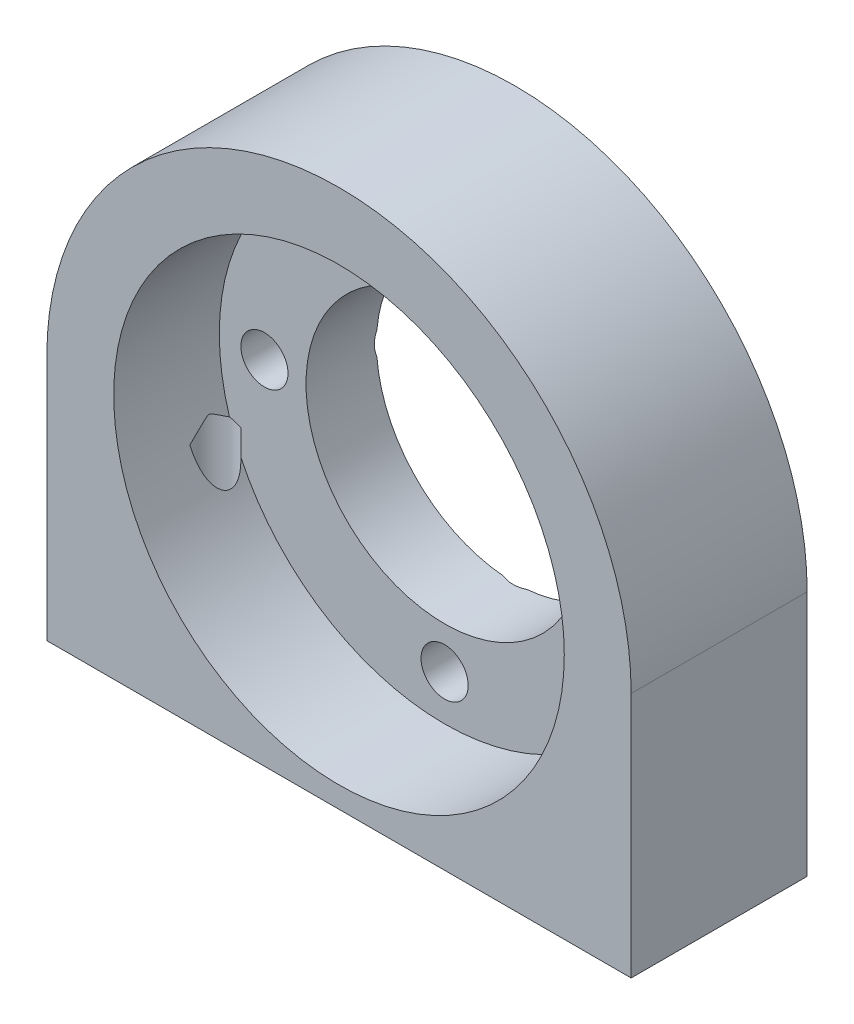
SolidWorks part; units mm, degrees
material "6061 Alloy"
ref_plane "Front Plane" through (0, 0, 0) normal (0, 0, 1) x (1, 0, 0)
ref_plane "Top Plane" through (0, 0, 0) normal (0, 1, 0) x (1, 0, 0)
ref_plane "Right Plane" through (0, 0, 0) normal (1, 0, 0) x (0, 0, -1)
sketch "Sketch1" plane through (0, 0, 0) normal (0, 0, 1) x (1, 0, 0)
  line L0 (-21.08, 0) -> (-21.08, -17.78)
  line L1 (-21.08, -17.78) -> (21.08, -17.78)
  line L2 (21.08, -17.78) -> (21.08, 0)
  circle A0 centre (0, 0) radius 16 construction
  arc A1 (21.08, 0) -> (-21.08, 0) centre (0, 0) ccw
  dimension "D1" = 32
  dimension "D2" = 5.08
  dimension "D3" = 17.78
extrude "Boss-Extrude1" add sketch "Sketch1" along normal mid plane 12.7
sketch "Sketch2" plane through (0, 0, 6.35) normal (0, 0, 1) x (1, 0, 0)
  circle A0 centre (0, 0) radius 16.256
  dimension "D1" = 32.512
extrude "Cut-Extrude1" cut sketch "Sketch2" against normal offset from surface (7.62 mm away) 5.08 up to face at (0, -3.62, -6.35)
sketch "Sketch3" plane through (0, 0, -1.27) normal (0, 0, 1) x (1, 0, 0)
  circle A0 centre (0, 0) radius 10
  dimension "D1" = 20
extrude "Cut-Extrude2" cut sketch "Sketch3" against normal through all
hole_wizard "CSK for M3 Flat Head Machine Screw1" positions "Sketch5" profile "Sketch6" countersink size "M3" standard "Ansi Metric" end condition through all
sketch "Sketch5" plane through (0, 0, -6.35) normal (0, 0, -1) x (-1, 0, 0)
  point P0 (0, 13)
  dimension "D1" = 13
sketch "Sketch6" plane through (0, 13, -6.35) normal (1, 0, 0) x (0, 1, 0)
  line L0 (0, 0) -> (0, 12.7)
  line L1 (0, 12.7) -> (1.7, 12.7)
  line L2 (1.7, 12.7) -> (1.7, 1.45)
  line L3 (1.7, 1.45) -> (3.15, 0)
  line L5 (3.15, 0) -> (0, 0)
  line L6 (-1.7, 1.45) -> (-3.15, 0) construction
  line L11 (0, -6.35) -> (0, 107.95) construction
  dimension "Thru Hole Dia." = 3.4
  dimension "Thru Hole Depth" = 12.7
  dimension "Near C'Sink Dia." = 6.3
  dimension "Near C'Sink Angle" = 90
pattern_circular "CirPattern1" count 4 over 360 about axis through (0, 0, -6.35) along (0, 0, 1) of "CSK for M3 Flat Head Machine Screw1"
hole_wizard "#8-32 Tapped Hole1" positions "Sketch8" profile "Sketch9" tap size "#8-32" standard "Ansi Inch"
sketch "Sketch8" plane through (0, -17.78, 0) normal (0, -1, 0) x (1, 0, 0)
  line L0 (-15.875, 0) -> (15.875, 0) construction
  point P0 (15.875, 0)
  point P7 (0, 0)
  point P9 (-15.875, 0)
  dimension "D1" = 31.75
sketch "Sketch9" plane through (15.875, -17.78, 0) normal (1, 0, 0) x (0, 0, -1)
  line L0 (0, 0) -> (0, 13.7378)
  line L1 (0, 13.7378) -> (1.7272, 12.7)
  line L2 (1.7272, 12.7) -> (1.7272, 0)
  line L5 (1.7272, 0) -> (0, 0)
  line L10 (0, 13.7378) -> (-1.7272, 12.7) construction
  line L11 (0, -6.35) -> (0, 107.95) construction
  dimension "Tap Drill Dia." = 3.4544
  dimension "Tap Drill Depth" = 12.7
  dimension "Drill Angle" = 118
